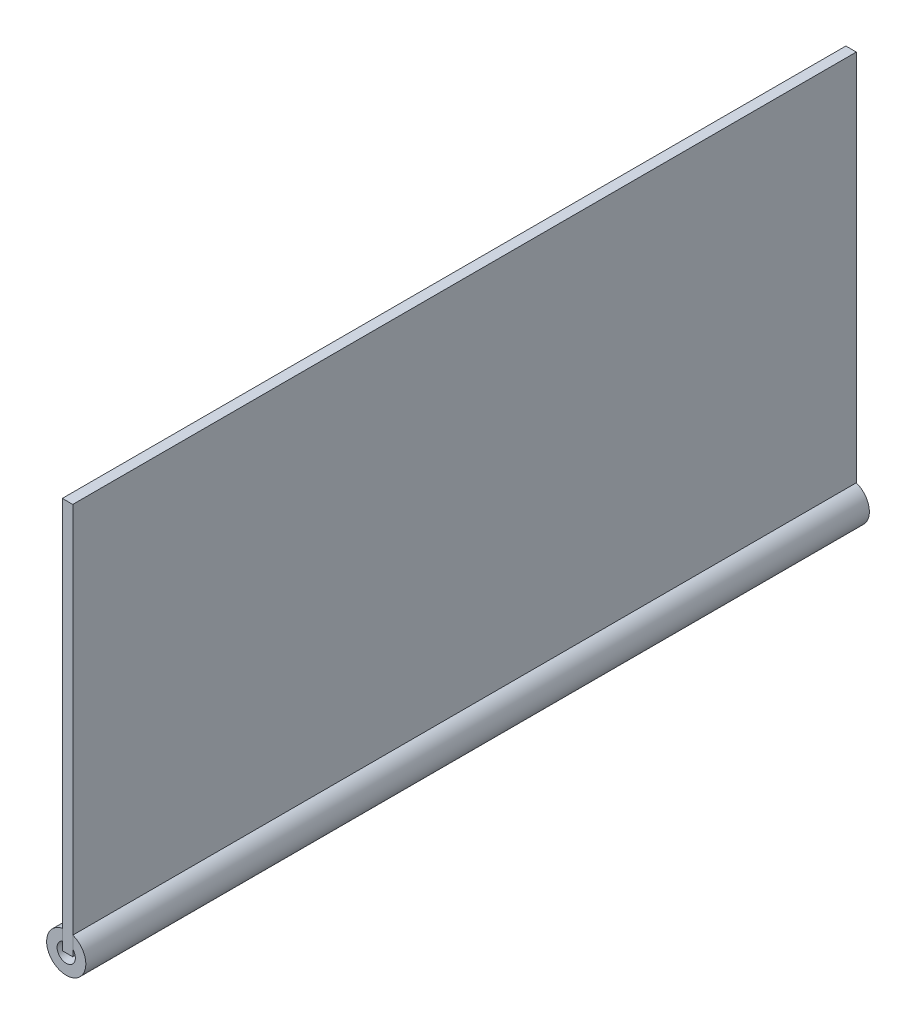
SolidWorks part; units mm, degrees
note: '?' marks a value the reader was unsure of.
other "COLL.BOX-Estrusione-Estrusione2"
ref_plane "Piano frontale" through (0, 0, 0) normal (0, 0, 1) x (1, 0, 0)
ref_plane "Piano superiore" through (0, 0, 0) normal (0, 1, 0) x (1, 0, 0)
ref_plane "Piano destro" through (0, 0, 0) normal (1, 0, 0) x (0, 0, -1)
sketch "Schizzo1" plane through (0, 0, 0) normal (1, 0, 0) x (0, 0, -1)
  line L1 (-150, -74.9) -> (150, -74.9)
  line L2 (-150, -74.9) -> (-150, 74.9)
  line L3 (-150, 74.9) -> (150, 74.9)
  line L4 (150, -74.9) -> (150, 74.9)
  line L5 (-150, -74.9) -> (150, 74.9) construction
  line L6 (-150, 74.9) -> (150, -74.9) construction
  point P0 (0, 0)
  dimension "D1" = 300
  dimension "D2" = 149.8
extrude "Estrusione-Estrusione1" add sketch "Schizzo1" along normal blind 3
sketch "Schizzo2" plane through (0, 0, 150) normal (0, 0, 1) x (1, 0, 0)
  line L0 (3, -74.9) -> (0, -74.9) construction
  circle A0 centre (1.5, -74.9) radius 7.5
  dimension "D1" = 15
sweep "Sweep1" add profiles "Schizzo2" path edge at (3, -74.9, 0)
sketch "Schizzo3" plane through (0, 0, 150) normal (0, 0, 1) x (1, 0, 0)
  circle A0 centre (1.5, -74.9) radius 3.5
  dimension "D1" = 7
extrude "Taglio-Estrusione1" cut sketch "Schizzo3" against normal through all
ref_axis "Assi1" through (1.5, -74.9, -150) along (0, 0, 1)?
sketch "Schizzo4" plane through (0, 0, 0) normal (1, 0, 0) x (0, 0, -1)
  line L1 (-150, 75) -> (150, 75)
  line L2 (-150, 75) -> (-150, -75)
  line L3 (-150, -75) -> (150, -75)
  line L4 (150, 75) -> (150, -75)
  line L5 (-150, 75) -> (150, -75) construction
  line L6 (-150, -75) -> (150, 75) construction
  point P0 (0, 0)
  dimension "D1" = 300
  dimension "D2" = 150
extrude "Estrusione-Estrusione2" add sketch "Schizzo4" along normal blind 4 separate body
sketch "Schizzo5" plane through (0, 0, 0) normal (0, 0, 1) x (1, 0, 0)
